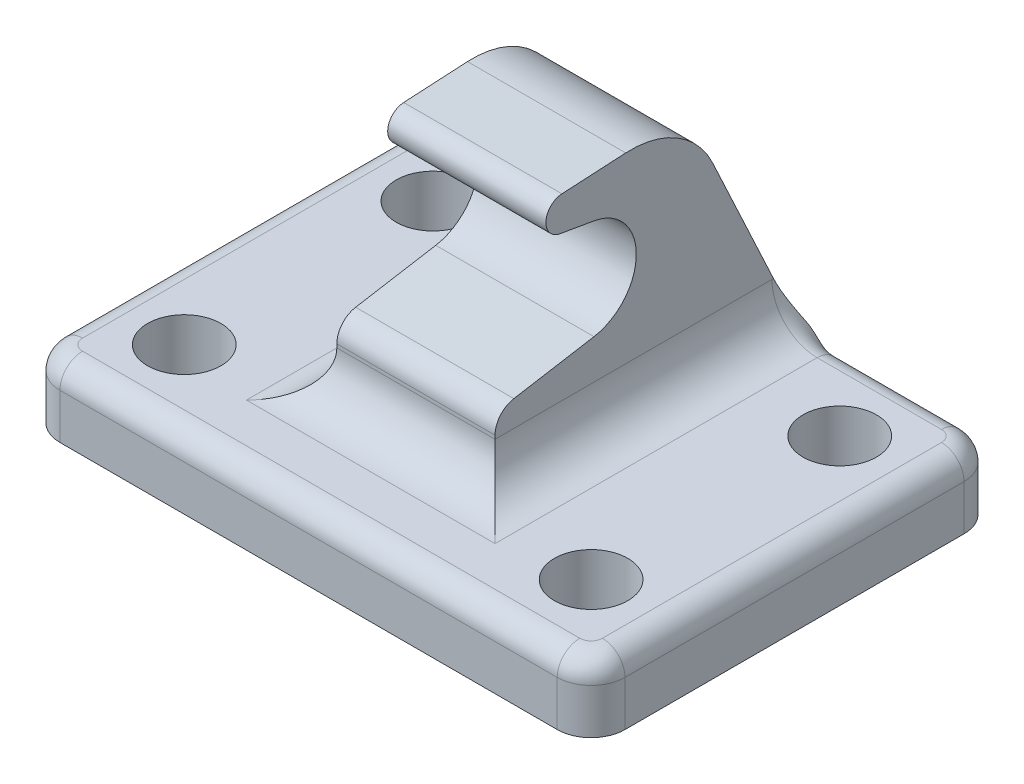
SolidWorks part; units mm, degrees
ref_plane "front" through (0, 0, 0) normal (0, 0, 1) x (1, 0, 0)
ref_plane "top" through (0, 0, 0) normal (0, 1, 0) x (1, 0, 0)
ref_plane "right" through (0, 0, 0) normal (1, 0, 0) x (0, 0, -1)
other "Configuration Table"
sketch "Sketch1" plane through (0, 0, 0) normal (0, 1, 0) x (1, 0, 0)
  line L1 (0, 0) -> (79.375, 0)
  line L2 (0, 0) -> (0, 57.15)
  line L3 (0, 57.15) -> (79.375, 57.15)
  line L4 (79.375, 0) -> (79.375, 57.15)
  dimension "D1" = 79.375
  dimension "D2" = 57.15
extrude "Base-Extrude" add sketch "Sketch1" along normal blind 9.525
sketch "Sketch2" plane through (0, 9.525, 0) normal (0, 1, 0) x (-1, 0, 0)
  line L0 (0, -57.15) -> (0, 0) construction
  line L1 (0, 0) -> (-79.375, 0) construction
  circle A0 centre (-11.1125, -46.0375) radius 5.1562
  circle A1 centre (-11.1125, -11.1125) radius 5.1562
  circle A2 centre (-68.2625, -11.1125) radius 5.1562
  circle A3 centre (-68.2625, -46.0375) radius 5.1562
  dimension "D1" = 10.3124
  dimension "D2" = 34.925
  dimension "D3" = 57.15
  dimension "D4" = 11.1125
  dimension "D5" = 11.1125
extrude "Cut-Extrude1" cut sketch "Sketch2" against normal through all
ref_plane "Plane4" through (39.6875, 0, 0) normal (1, 0, 0) x (0, 0, -1)
sketch "Sketch3" plane through (39.6875, 0, 0) normal (1, 0, 0) x (0, 0, -1)
  line L0 (0, 9.525) -> (57.15, 9.525) construction
  line L1 (15.0812, 9.525) -> (57.15, 9.525)
  line L2 (57.15, 9.525) -> (45.6421, 34.2125)
  line L3 (33.436, 41.5277) -> (24.4759, 41.0365)
  line L4 (24.2027, 36.312) -> (28.992, 35.4884)
  line L5 (28.9749, 21.4047) -> (17.7257, 19.4982)
  line L6 (15.0812, 16.3678) -> (15.0812, 9.525)
  line L7 (0, 9.525) -> (0, 0) construction
  arc A0 (24.4759, 41.0365) -> (24.2027, 36.312) centre (24.6062, 38.6588) ccw
  arc A1 (28.992, 35.4884) -> (28.9749, 21.4047) centre (27.7812, 28.448) cw
  arc A2 (33.436, 41.5277) -> (45.6421, 34.2125) centre (34.1313, 28.8468) cw
  arc A3 (15.0812, 16.3678) -> (17.7257, 19.4982) centre (18.2562, 16.3678) cw
  point P18 (15.0812, 19.05)
  dimension "D1" = 12.7
  dimension "D2" = 2.3813
  dimension "D3" = 7.1437
  dimension "D5" = 29.1338
  dimension "D6" = 34.1313
  dimension "D7" = 19.3218
  dimension "D9" = 18.923
  dimension "D12" = 3.175
  dimension "D4" = 24.6062
  dimension "D8" = 27.7812
  dimension "D10" = 15.0812
  dimension "D11" = 9.525
extrude "Boss-Extrude1" add sketch "Sketch3" along normal mid plane 22.225
fillet "Fillet1" radius 4.7625 4 edges at (0, 4.7625, 0) (79.375, 4.7625, 0) (0, 4.7625, -57.15) (79.375, 4.7625, -57.15)
fillet "Fillet3" radius 3.175 9 edges at (1.3949, 9.525, -55.7551) (77.9801, 9.525, -55.7551) (0, 9.525, -28.575) (79.375, 9.525, -28.575) (1.3949, 9.525, -1.3949) (77.9801, 9.525, -1.3949) (39.6875, 9.525, 0)
fillet "Fillet5" radius 6.35 5 edges at (50.8, 8.5951, -56.2201) (28.575, 8.5951, -56.2201) (39.6875, 9.525, -15.0812)
fillet "Fillet6" radius 3.175 1 edges
